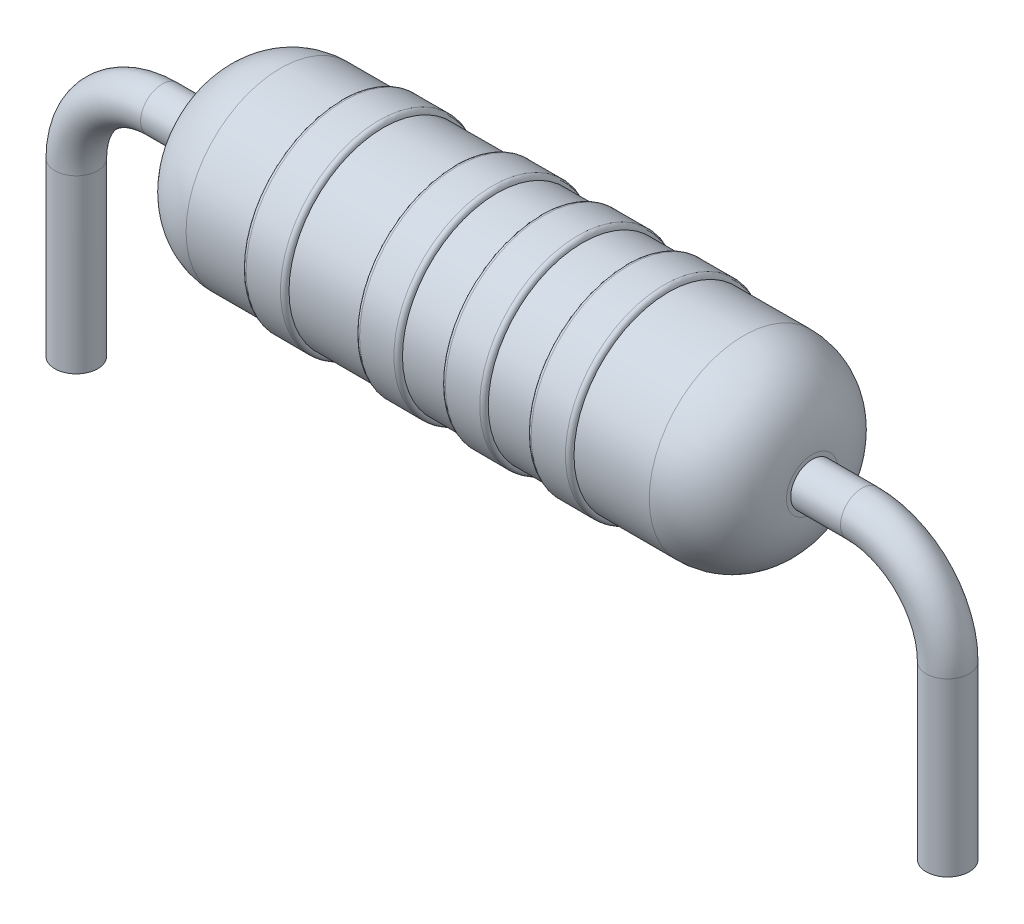
SolidWorks part; units mm, degrees
ref_plane "Face" through (0, 0, 0) normal (0, 0, 1) x (1, 0, 0)
ref_plane "Dessus" through (0, 0, 0) normal (0, 1, 0) x (1, 0, 0)
ref_plane "Droite" through (0, 0, 0) normal (1, 0, 0) x (0, 0, -1)
sketch "Esquisse1" plane through (0, 0, 0) normal (0, 0, 1) x (1, 0, 0)
  line L0 (-54.2687, 0) -> (62.1733, 0) construction
  line L1 (-48.4922, 1.1) -> (45.7559, 1.1) construction
  line L2 (-3.5, -1.6411) -> (-3.5, 4.3175) construction
  line L3 (0, -1.0268) -> (0, 4.1947) construction
  line L4 (3.5, 3.6009) -> (3.5, -1.9687) construction
  line L5 (-3.5, 0) -> (-3.5, 0.3)
  line L6 (-2.7, 1.1) -> (2.7, 1.1)
  line L7 (3.5, 0.3) -> (3.5, 0)
  line L8 (3.5, 0) -> (-3.5, 0)
  arc A0 (-2.7, 1.1) -> (-3.5, 0.3) centre (-2.7, 0.3) ccw
  arc A1 (3.5, 0.3) -> (2.7, 1.1) centre (2.7, 0.3) ccw
revolve "Base-Révolution" add sketch "Esquisse1" angle 360 about L0
sketch "Esquisse2" plane through (0, 0, 0) normal (0, 0, 1) x (1, 0, 0)
  line L0 (-3.3896, 1.15) -> (3.161, 1.15) construction
  line L1 (-2, 1.3889) -> (-2, -0.1179) construction
  line L2 (-1.5, 1.4925) -> (-1.5, -0.2136) construction
  line L3 (4.3262, 0) -> (-3.8651, 0) construction
  line L4 (1.323, 0) -> (1.823, 0)
  line L5 (0.323, 0) -> (0.823, 0)
  line L6 (-0.677, 1.15) -> (-0.677, 0)
  line L7 (0.323, 1.15) -> (0.323, 0)
  line L8 (1.323, 1.15) -> (1.323, 0)
  line L9 (-0.177, 1.15) -> (-0.177, 0)
  line L10 (0.823, 1.15) -> (0.823, 0)
  line L11 (1.823, 1.15) -> (1.823, 0)
  line L12 (-0.677, 0) -> (-0.177, 0)
  line L13 (-0.677, 1.15) -> (-0.177, 1.15)
  line L14 (0.323, 1.15) -> (0.823, 1.15)
  line L15 (1.323, 1.15) -> (1.823, 1.15)
  line L16 (-2, 1.15) -> (-1.5, 1.15)
  line L17 (-1.5, 1.15) -> (-1.5, 0)
  line L18 (-1.5, 0) -> (-2, 0)
  line L19 (-2, 0) -> (-2, 1.15)
revolve "Boss.-Révol.1" add sketch "Esquisse2" angle 360 about L3
fillet "Congé1" radius 0.05 8 edges at (-2, 0, -1.15) (-1.5, 0, -1.15) (-0.677, 0, -1.15) (-0.177, 0, -1.15) (0.323, 0, -1.15) (0.823, 0, -1.15) (1.323, 0, -1.15) (1.823, 0, -1.15)
sketch "Esquisse3" plane through (-3.5, 0, 0) normal (-1, 0, 0) x (0, 0, 1)
  circle A0 centre (0, 0) radius 0.25
sketch "Esquisse4" plane through (0, 0, 0) normal (0, 0, 1) x (1, 0, 0)
  line L0 (-3.1075, 0) -> (-5.8186, 0) construction
  line L1 (0, -2.524) -> (0, 3.2043) construction
  line L2 (-5.9326, -3) -> (3.6667, -3) construction
  line L3 (-5.08, 1.6795) -> (-5.08, -3.4934) construction
  line L4 (-3.08, 0) -> (-4.08, 0)
  line L5 (-5.08, -1) -> (-5.08, -3)
  arc A0 (-4.08, 0) -> (-5.08, -1) centre (-4.08, -1) ccw
  dimension "D1" = 3
  dimension "D2" = 5.08
sweep "Balayage1" add profiles "Esquisse3" path "Esquisse4"
ref_plane "Plan1" through (0, 0, 0) normal (1, 0, 0) x (0, 0, -1)
mirror "Symétrie1" about plane through (0, 0, 0) normal (1, 0, 0) of "Balayage1"
